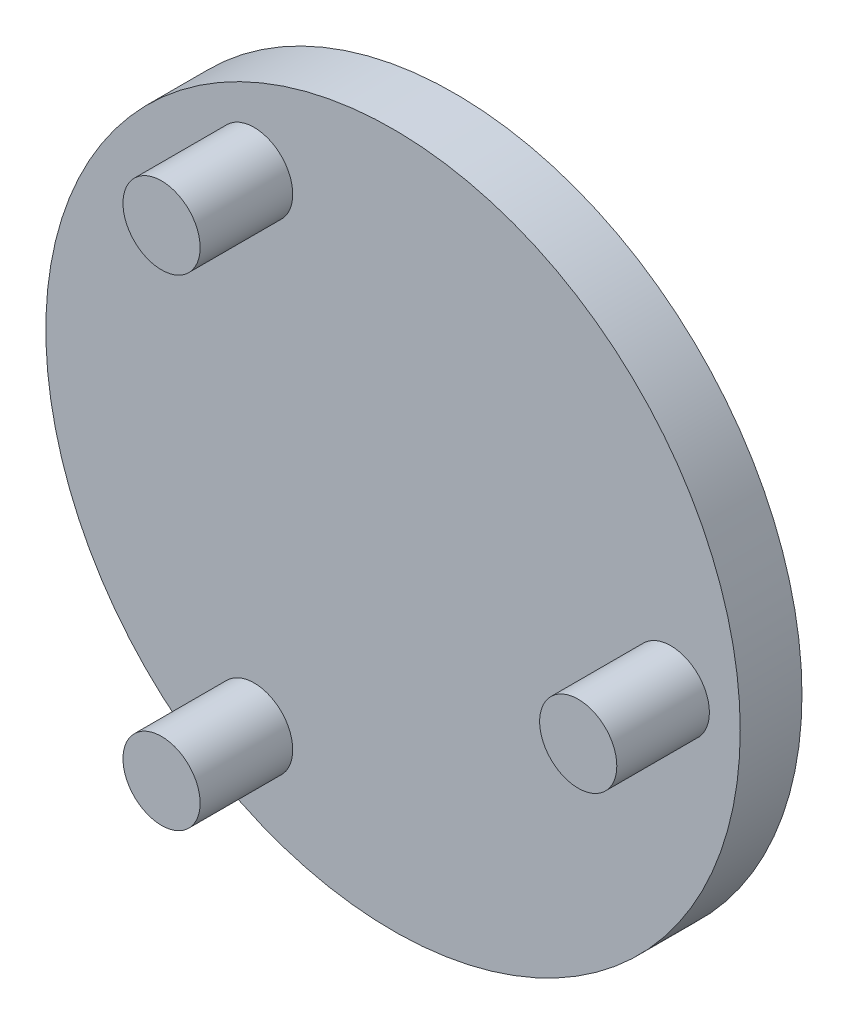
SolidWorks part; units mm, degrees
ref_plane "前视基准面" through (0, 0, 0) normal (0, 0, 1) x (1, 0, 0)
ref_plane "上视基准面" through (0, 0, 0) normal (0, 1, 0) x (1, 0, 0)
ref_plane "右视基准面" through (0, 0, 0) normal (1, 0, 0) x (0, 0, -1)
other "Configuration Table"
sketch "Sketch1" plane through (0, 0, 0) normal (0, 0, 1) x (1, 0, 0)
  circle A0 centre (0, 0) radius 45
extrude "Boss-Extrude1" add sketch "Sketch1" along normal blind 8
ref_plane "Plane1" through (0, 0, 8) normal (0, 0, 1) x (1, 0, 0)
sketch "Sketch2" plane through (0, 0, 8) normal (0, 0, 1) x (1, 0, 0)
  circle A0 centre (36, 0) radius 5
  circle A1 centre (-18, 31.1769) radius 5
  circle A2 centre (-18, -31.1769) radius 5
extrude "Boss-Extrude2" add sketch "Sketch2" along normal blind 12
sketch3d "3DSketch1"
  line L0 (0, 0, 0) -> (0, 0, 8) construction
ref_axis "output_axis" through (0, 0, 0) along (0, 0, 1)
sketch3d "3DSketch2"
  line L0 (36, 0, 8) -> (36, 0, 20) construction
ref_axis "pin_1_axis" through (36, 0, 8) along (0, 0, 1)
sketch3d "3DSketch3"
  line L0 (-18, 31.1769, 8) -> (-18, 31.1769, 20) construction
ref_axis "pin_2_axis" through (-18, 31.1769, 8) along (0, 0, 1)
sketch3d "3DSketch4"
  line L0 (-18, -31.1769, 8) -> (-18, -31.1769, 20) construction
ref_axis "pin_3_axis" through (-18, -31.1769, 8) along (0, 0, 1)
ref_plane "base_face" through (0, 0, 0) normal (0, 0, 1) x (1, 0, 0)
